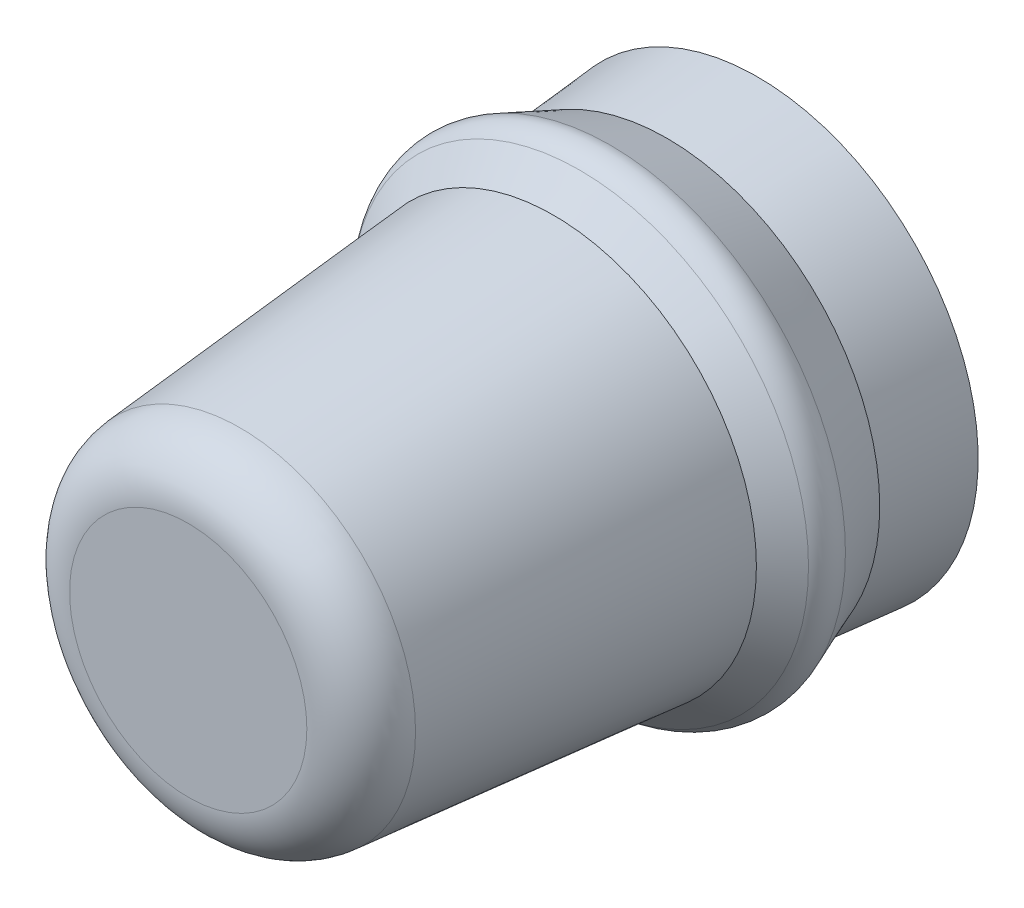
SolidWorks part; units mm, degrees
ref_plane "Front Plane" through (0, 0, 0) normal (1, 0, 0) x (0, 1, 0)
ref_plane "Top Plane" through (0, 0, 0) normal (0, 0, 1) x (0, 1, 0)
ref_plane "Right Plane" through (0, 0, 0) normal (0, 1, 0) x (-1, 0, 0)
sketch "Sketch1" plane through (0, 0, 0) normal (1, 0, 0) x (0, 1, 0)
  line L1 (0, 0) -> (2, 0)
  line L2 (0, 0) -> (0, 5)
  line L3 (0, 5) -> (2, 5)
  line L4 (2, 0) -> (2, 5)
  dimension "D1" = 2
  dimension "D2" = 5
revolve "Revolve1" add sketch "Sketch1" angle 360 about L2
chamfer "Chamfer1" distance 0.5 angle 85 1 edges at (-2, 0, 5) first distance on face at (-2, 0, 5)
fillet "Fillet1" radius 0.5 1 edges at (1.5, 0, 5)
sketch "Sketch2" plane through (0, 0, 0) normal (1, 0, 0) x (0, 1, 0)
  line L0 (1.8679, 0.7951) -> (2.1256, 1.4461)
  line L1 (1.9374, 0) -> (1.5399, 4.5436) construction
  line L2 (2.1256, 1.4461) -> (1.7808, 1.791)
  line L3 (1.7808, 1.791) -> (1.8679, 0.7951)
ref_axis "Axis1" through (0, 0, 0) along (0, 0, 1)
revolve "Revolve3" add sketch "Sketch2" angle 360 about axis through (0, 0, 0) along (0, 0, 1)
fillet "Fillet2" radius 0.25 1 edges at (-2.1256, 0, 1.4461)
